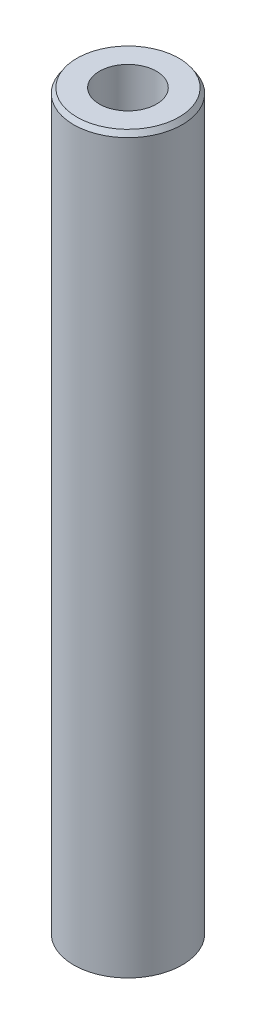
SolidWorks part; units mm, degrees
ref_plane "Front Plane" through (0, 0, 0) normal (0, 0, 1) x (1, 0, 0)
ref_plane "Top Plane" through (0, 0, 0) normal (0, 1, 0) x (1, 0, 0)
ref_plane "Right Plane" through (0, 0, 0) normal (1, 0, 0) x (0, 0, -1)
sketch "Sketch1" plane through (0, 0, 0) normal (0, 1, 0) x (1, 0, 0)
  circle A0 centre (0, 0) radius 7.5
  dimension "SHAFT_OD" = 15
extrude "Boss-Extrude1" add sketch "Sketch1" along normal blind 101.7164
sketch "Sketch2" plane through (0, 0, 0) normal (0, 1, 0) x (1, 0, 0)
  circle A0 centre (0, 0) radius 3.9437
  dimension "BORE_D" = 7.8873
extrude "Cut-Extrude1" cut sketch "Sketch2" along normal through all
chamfer "Chamfer1" distance 0.6865 angle 33.022 2 edges at (0, 101.7164, 7.5) (0, 0, 7.5) first distance on face at (0, 101.7164, 7.5) first distance on face at (0, 0, 3.9437)
